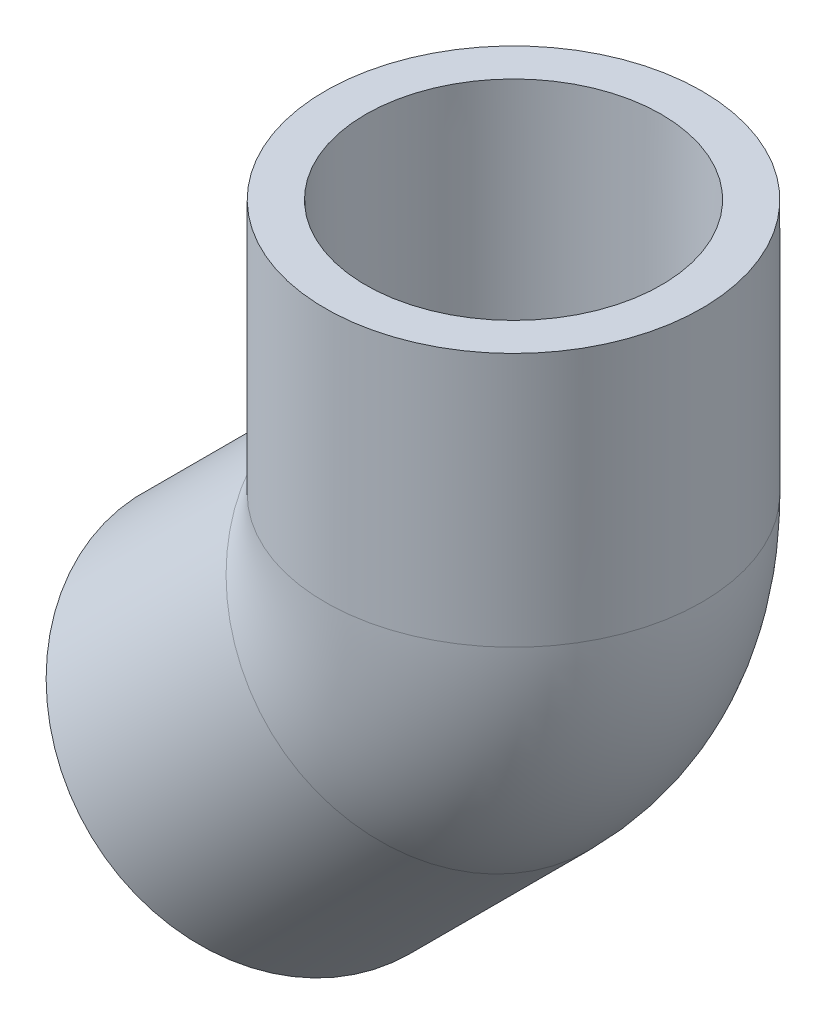
SolidWorks part; units mm, degrees
ref_plane "Front Plane" through (0, 0, 0) normal (0, 0, 1) x (1, 0, 0)
ref_plane "Top Plane" through (0, 0, 0) normal (0, 1, 0) x (1, 0, 0)
ref_plane "Right Plane" through (0, 0, 0) normal (1, 0, 0) x (0, 0, -1)
sketch "Sketch0" plane through (0, 0, 0) normal (0, 0, 1) x (1, 0, 0)
  line L0 (-26.9408, -26.9408) -> (0, 0) construction
  line L1 (0, 0) -> (0, 38.1) construction
  line L2 (-6.4658, -6.4658) -> (0, 0) construction
  line L3 (0, 0) -> (0, 9.144) construction
  line L4 (-42.095, -11.7866) -> (-11.7866, -42.095) construction
  line L5 (-18.2299, 5.2984) -> (-38.8396, -15.0419) construction
  line L6 (-18.2299, 5.2984) -> (5.2984, -18.2299) construction
  line L7 (5.2984, -18.2299) -> (-15.0419, -38.8396) construction
  line L8 (-38.8396, -15.0419) -> (-15.0419, -38.8396) construction
  line L9 (-21.4312, 38.1) -> (21.4312, 38.1) construction
  line L10 (-16.8275, 38.1) -> (16.8275, 38.1) construction
  line L11 (16.8275, 38.1) -> (16.637, 9.144) construction
  line L12 (16.637, 9.144) -> (-16.637, 9.144) construction
  line L13 (-16.637, 9.144) -> (-16.8275, 38.1) construction
  line L14 (-15.0599, 2.1283) -> (2.1283, -15.0599) construction
  line L18 (-12.1539, 9.144) -> (12.1539, 9.144) construction
  dimension "D1" = 45
  dimension "H" = 38.1
  dimension "J" = 9.144
  dimension "M" = 42.8625
  dimension "OD A" = 33.655
  dimension "OD B" = 33.274
  dimension "ID" = 24.3078
sketch "Sketch1" plane through (0, 0, 0) normal (0, 0, 1) x (1, 0, 0)
  line L0 (-26.9408, -26.9408) -> (0, 0) construction
  line L1 (-26.9408, -26.9408) -> (0, 0) construction
  line L3 (-11.7866, -42.095) -> (8.6884, -21.62)
  line L4 (-11.7866, -42.095) -> (-15.0419, -38.8396)
  line L5 (-15.0419, -38.8396) -> (5.2984, -18.2299)
  line L6 (8.6884, -21.62) -> (5.2984, -18.2299)
revolve "Revolve1" add sketch "Sketch1" angle 360 about L1
sketch "Sketch2" plane through (0, 0, 0) normal (0, 0, 1) x (1, 0, 0)
  line L0 (16.8275, 38.1) -> (16.637, 9.144)
  line L1 (16.637, 9.144) -> (21.4312, 9.144)
  line L2 (21.4312, 9.144) -> (21.4312, 38.1)
  line L3 (21.4312, 38.1) -> (16.8275, 38.1)
  line L4 (0, 0) -> (0, 38.1) construction
  line L5 (0, 0) -> (0, 38.1) construction
revolve "Revolve2" add sketch "Sketch2" angle 360 about L5
sketch "Sketch3" plane through (-6.4658, -6.4658, 0) normal (0.7071, 0.7071, 0) x (0, 0, -1)
  circle A0 centre (0, 0) radius 12.1539
  circle A1 centre (0, 0) radius 21.4312 construction
  circle A4 centre (0, 0) radius 21.4312
sketch "Sketch4" plane through (0, 0, 0) normal (0, 0, 1) x (1, 0, 0)
  line L0 (-26.9408, -26.9408) -> (0, 0) construction
  line L1 (0, 0) -> (0, 38.1) construction
  line L2 (-26.9408, -26.9408) -> (-6.4658, -6.4658) construction
  line L3 (0, 9.144) -> (0, 38.1) construction
  arc A0 (-6.4658, -6.4658) -> (0, 9.144) centre (-22.0756, 9.144) ccw
sweep "Sweep1" add profiles "Sketch3" path "Sketch4"
other "CPoint1" parameters "Diameter"=25.4, "StubLength"=114.3
ref_axis "Axis1" through (-13.5369, -13.5369, 0) along (0.7071, 0.7071, 0)
other "CPoint2" parameters "Diameter"=25.4, "StubLength"=38.1
ref_axis "Axis2" through (0, 19.144, 0) along (0, -1, 0)
other "RPoint1"
